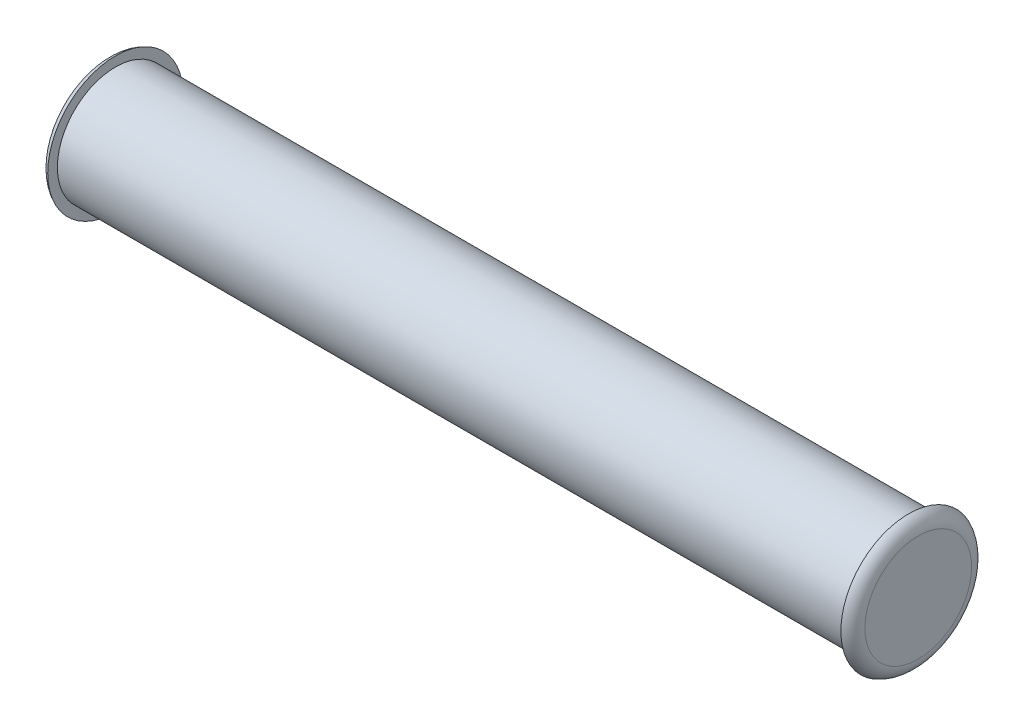
SolidWorks part; units mm, degrees
ref_plane "Front Plane" through (0, 0, 0) normal (0, 0, 1) x (1, 0, 0)
ref_plane "Top Plane" through (0, 0, 0) normal (0, 1, 0) x (1, 0, 0)
ref_plane "Right Plane" through (0, 0, 0) normal (1, 0, 0) x (0, 0, -1)
sketch "Sketch1" plane through (0, 0, 0) normal (1, 0, 0) x (0, 0, -1)
  circle A0 centre (0, 0) radius 0.762
  dimension "D1" = 1.524
extrude "Extrude1" add sketch "Sketch1" along normal blind 10.414
sketch "Sketch2" plane through (10.414, 0, 0) normal (1, 0, 0) x (0, 0, -1)
  circle A0 centre (0, 0) radius 0.889
  dimension "D1" = 1.778
extrude "Extrude2" add sketch "Sketch2" along normal blind 0.127
sketch "Sketch3" plane through (0, 0, 0) normal (-1, 0, 0) x (0, 0, 1)
  circle A0 centre (0, 0) radius 0.889
  dimension "D1" = 1.778
extrude "Extrude3" add sketch "Sketch3" along normal blind 0.127
fillet "Fillet1" radius 0.2032 2 edges at (10.541, 0, -0.889) (-0.127, 0, 0.889)
